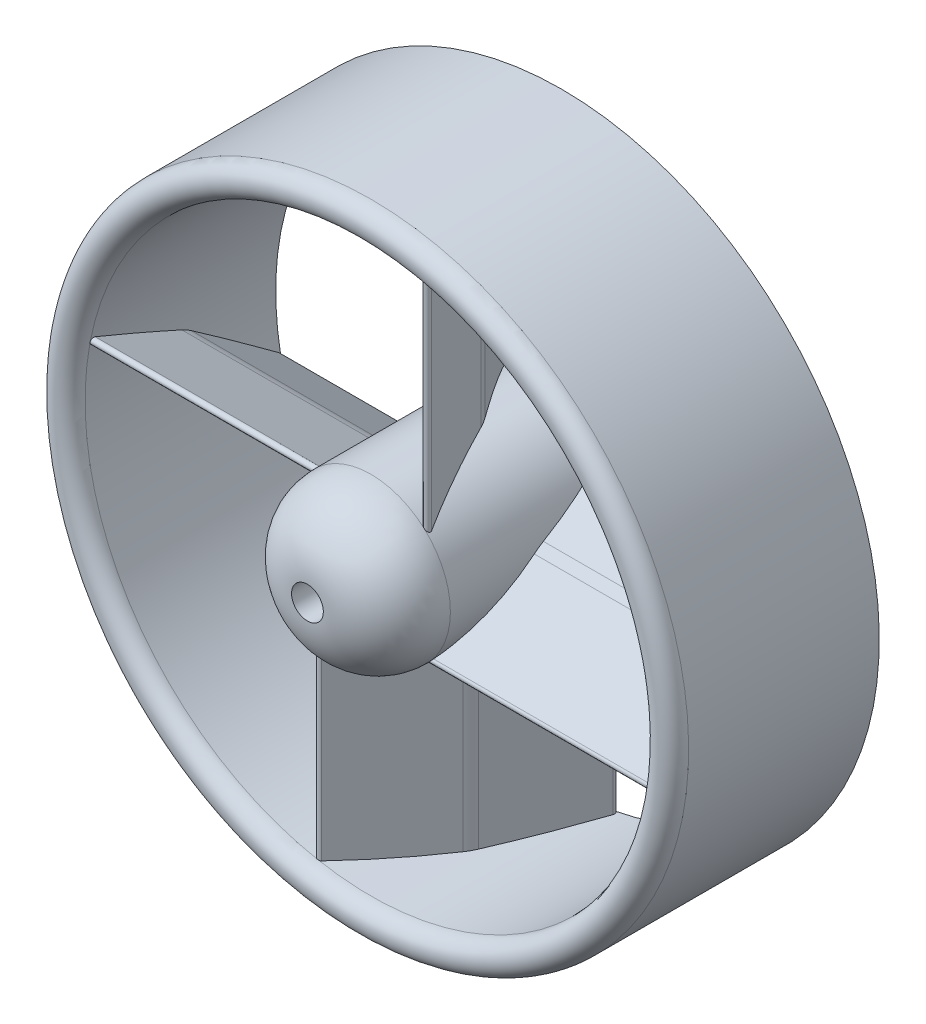
SolidWorks part; units mm, degrees
ref_plane "前视基准面" through (0, 0, 0) normal (0, 0, 1) x (1, 0, 0)
ref_plane "上视基准面" through (0, 0, 0) normal (0, 1, 0) x (1, 0, 0)
ref_plane "右视基准面" through (0, 0, 0) normal (1, 0, 0) x (0, 0, -1)
other "Configuration Table"
sketch "草图3" plane through (0, 0, 0) normal (1, 0, 0) x (0, 0, -1)
  line L0 (-30, 45) -> (0, 45)
  line L1 (-30, 50) -> (0, 50)
  line L2 (0, 45) -> (0, 50)
  line L3 (-30, 45) -> (-30, 50) construction
  line L4 (0, 0) -> (-18.5697, 0) construction
  line L5 (-30, 2.5) -> (-40, 2.5)
  line L6 (0, 12.5) -> (-30, 12.5)
  line L7 (0, 12.5) -> (0, 2.5)
  line L8 (0, 2.5) -> (-30, 2.5)
  line L9 (-30, 12.5) -> (-30, 2.5) construction
  arc A0 (-30, 50) -> (-30, 45) centre (-30, 47.5) ccw
  arc A1 (-30, 12.5) -> (-40, 2.5) centre (-30, 2.5) ccw
  point P13 (0, 0)
  point P14 (-25.9982, 2.5)
  dimension "D1" = 45
  dimension "D2" = 50
  dimension "D3" = 30
  dimension "D4" = 30
  dimension "D5" = 2.5
  dimension "D6" = 10
revolve "旋转1" add sketch "草图3" angle 360 about L4
sketch "草图6" plane through (0, 0, 0) normal (1, 0, 0) x (0, 0, -1)
  line L0 (-40, 2.5) -> (-31.7484, 2.5) construction
  line L1 (-40, -2.5) -> (-35.47, -2.5) construction
  line L2 (0, 0) -> (-30, 0) construction
  line L3 (-40, 2.5) -> (-40, -2.5) construction
  line L4 (-40, 2.5) -> (-40, -2.5) construction
  line L5 (-30, 12.5) -> (-30, -12.5) construction
  line L6 (-34.3591, -11.177) -> (4.3591, 11.177) construction
  line L8 (-16, 1.7321) -> (-14, -1.7321) construction
  line L9 (-29.7876, -7.9626) -> (-16.7319, 1.2174)
  line L10 (-15.1884, 2.1086) -> (-0.7104, 8.8251)
  line L11 (-0.2124, 7.9626) -> (-13.2681, -1.2174)
  line L12 (-29.2896, -8.8251) -> (-14.8116, -2.1086)
  arc A0 (-16.7319, 1.2174) -> (-15.1884, 2.1086) centre (-10.98, -6.9628) cw
  arc A1 (-13.2681, -1.2174) -> (-14.8116, -2.1086) centre (-19.02, 6.9628) cw
  arc A2 (-0.7104, 8.8251) -> (-0.2124, 7.9626) centre (-0.5, 8.3716) cw
  arc A3 (-29.7876, -7.9626) -> (-29.2896, -8.8251) centre (-29.5, -8.3716) ccw
  point P15 (-15, 0)
  point P30 (0, 0)
  point P31 (0, 0)
  dimension "D3" = 10
  dimension "D4" = 0.5
  dimension "D1" = 30
  dimension "D2" = 4
extrude "凸台-拉伸2" add sketch "草图6" along normal up to surface (40.9835 mm away) from offset 4 up to face at (0, 45, 0)
pattern_circular "阵列(圆周)1" count 4 over 360 about axis through (0, 0, 0) along (0, 0, -1) of "凸台-拉伸2"
